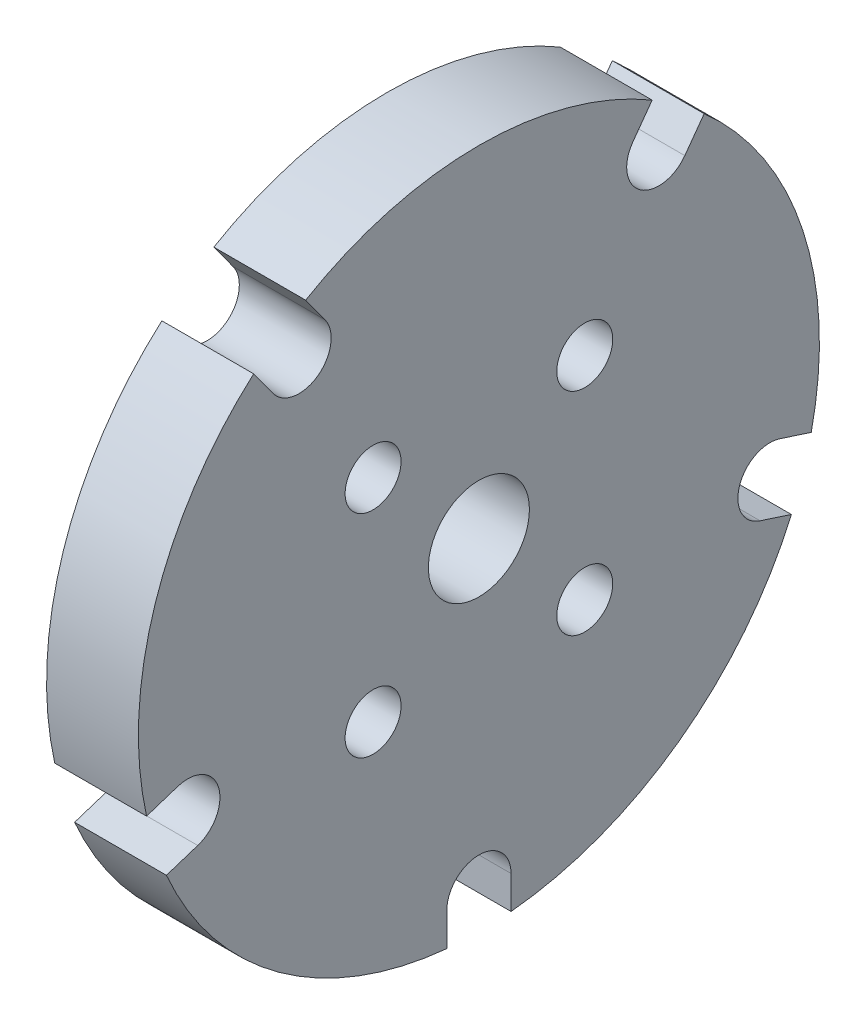
SolidWorks part; units mm, degrees
ref_plane "Plan de face" through (0, 0, 0) normal (0, 0, 1) x (1, 0, 0)
ref_plane "Plan de dessus" through (0, 0, 0) normal (0, 1, 0) x (1, 0, 0)
ref_plane "Plan de droite" through (0, 0, 0) normal (1, 0, 0) x (0, 0, -1)
sketch "Esquisse1" plane through (0, 0, 0) normal (1, 0, 0) x (0, 0, -1)
  circle A0 centre (0, 0) radius 22.25
  dimension "D1" = 44.5
extrude "Boss.-Extru.1" add sketch "Esquisse1" along normal blind 6
sketch "Esquisse5" plane through (6, 0, 0) normal (1, 0, 0) x (0, 0, -1)
  line L0 (0, -20) -> (0, -24.5) construction
  line L1 (2.1, -20) -> (2.1, -24.5)
  line L2 (-2.1, -20) -> (-2.1, -24.5)
  line L3 (0, 0) -> (0, -20) construction
  arc A0 (2.1, -20) -> (-2.1, -20) centre (0, -20) ccw
  arc A1 (-2.1, -24.5) -> (2.1, -24.5) centre (0, -24.5) ccw
  circle A2 centre (0, 0) radius 22.25 construction
  point P3 (0, -22.25)
  point P10 (0, 0)
  dimension "D2" = 4.2
  dimension "D1" = 20
extrude "Enlèv. mat.-Extru.1" cut sketch "Esquisse5" against normal up to next
pattern_circular "Répétition circulaire1" count 5 over 360 about axis through (6, 0, 0) along (1, 0, 0) of "Enlèv. mat.-Extru.1"
sketch "Esquisse6" plane through (6, 0, 0) normal (1, 0, 0) x (0, 0, -1)
  circle A0 centre (0, 0) radius 3.3
  dimension "D1" = 6.6
extrude "Enlèv. mat.-Extru.2" cut sketch "Esquisse6" against normal up to next
hole_wizard "Chambrage pour vis à tête ronde bombée #61" positions "Esquisse7" profile "Esquisse8" counterbore size "#6" standard "Ansi Inch" end condition through all
sketch "Esquisse7" plane through (0, 0, 0) normal (-1, 0, 0) x (0, 0, 1)
  line L0 (-6.9148, 6.9148) -> (-6.9148, -6.9148) construction
  line L1 (-6.9148, -6.9148) -> (6.9148, -6.9148) construction
  line L2 (6.9148, -6.9148) -> (6.9148, 6.9148) construction
  line L3 (6.9148, 6.9148) -> (-6.9148, 6.9148) construction
  line L5 (0, 6.9148) -> (0, 0) construction
  line L6 (0, 0) -> (-6.9148, 0) construction
  point P0 (-6.9148, 6.9148)
  point P2 (6.9148, 6.9148)
  point P4 (6.9148, -6.9148)
  point P6 (-6.9148, -6.9148)
  point P21 (-7.0035, -6.8249)
  dimension "D1" = 19.558
sketch "Esquisse8" plane through (0, 6.9148, -6.9148) normal (0, 1, 0) x (0, 0, 1)
  line L0 (0, 0) -> (0, 6)
  line L1 (0, 6) -> (1.8288, 6)
  line L3 (1.8288, 6) -> (1.8288, 2.4638)
  line L4 (1.8288, 2.4638) -> (3.7706, 2.4638)
  line L5 (3.7706, 2.4638) -> (3.7706, 0)
  line L7 (3.7706, 0) -> (0, 0)
  line L11 (0, -6.35) -> (0, 107.95) construction
  dimension "Diamètre du perçage jusqu'au prochain" = 3.6576
  dimension "Profondeur du perçage jusqu'au prochain" = 6
  dimension "Diamètre du chambrage" = 7.5413
  dimension "Profondeur du chambrage" = 2.4638
